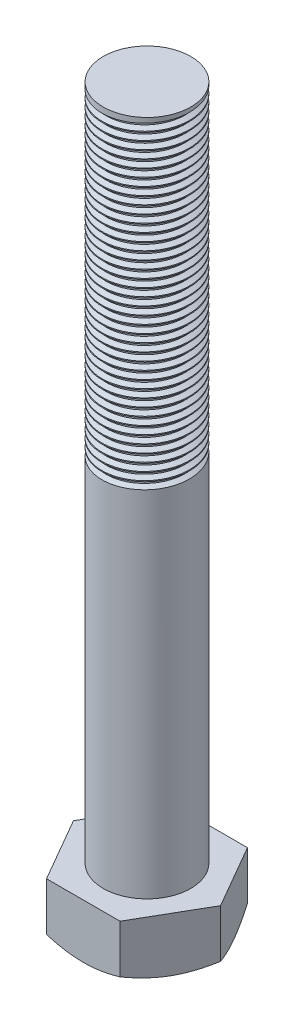
SolidWorks part; units mm, degrees
material "Alloy Steel"
ref_plane "Front Plane" through (0, 0, 0) normal (0, 0, 1) x (1, 0, 0)
ref_plane "Top Plane" through (0, 0, 0) normal (0, 1, 0) x (1, 0, 0)
ref_plane "Right Plane" through (0, 0, 0) normal (1, 0, 0) x (0, 0, -1)
sketch "Sketch1" plane through (0, 0, 0) normal (0, 1, 0) x (1, 0, 0)
  circle A0 centre (0, 0) radius 11
  dimension "D1" = 22
extrude "Boss-Extrude1" add sketch "Sketch1" along normal blind 170
thread "Thread1" pitch 2 method cut profile "Thread Profile1" start angle 0, offset 0, length 80, pitch 2, diameter 22
ref_plane "Plane1" through (-11, 170, 0) normal (0, 0, 1) x (-1, 0, 0)
sketch "Thread Profile1" plane through (-11, 170, 0) normal (0, 0, 1) x (-1, 0, 0)
  line L0 (0, 0) -> (0, 2) construction
  line L11 (0, 0) -> (0, 1.75)
  line L12 (0, 1.75) -> (-1.0825, 1.125)
  line L13 (-1.0825, 1.125) -> (-1.0825, 0.625)
  line L15 (-1.0825, 0.625) -> (0, 0)
  line L17 (-1.0825, 0.875) -> (0, 0.875) construction
  point P2 (0, 0)
  dimension "Pitch" = 2
  dimension "Profile_Angle" = 60
  dimension "Profile_Land" = 0.5
  dimension "Profile_Height" = 1.0825
sketch "Sketch6" plane through (0, 0, 0) normal (0, 1, 0) x (1, 0, 0)
  line L1 (18.4752, 0) -> (9.2376, 16)
  line L2 (9.2376, 16) -> (-9.2376, 16)
  line L3 (-9.2376, 16) -> (-18.4752, 0)
  line L4 (-18.4752, 0) -> (-9.2376, -16)
  line L5 (-9.2376, -16) -> (9.2376, -16)
  line L6 (9.2376, -16) -> (18.4752, 0)
  circle A0 centre (0, 0) radius 16 construction
  dimension "D1" = 32
extrude "Boss-Extrude2" add sketch "Sketch6" against normal blind 14
sketch "Sketch7" plane through (0, 0, 0) normal (0, 0, 1) x (1, 0, 0)
  line L0 (-19.4223, -11.5768) -> (-13.5212, -15.0275)
  line L1 (-13.5212, -15.0275) -> (-19.4223, -15.0275)
  line L2 (-19.4223, -15.0275) -> (-19.4223, -11.5768)
  line L3 (0, -8.1077) -> (0, -21.9154) construction
revolve "Cut-Revolve1" cut sketch "Sketch7" angle 360 about L3
